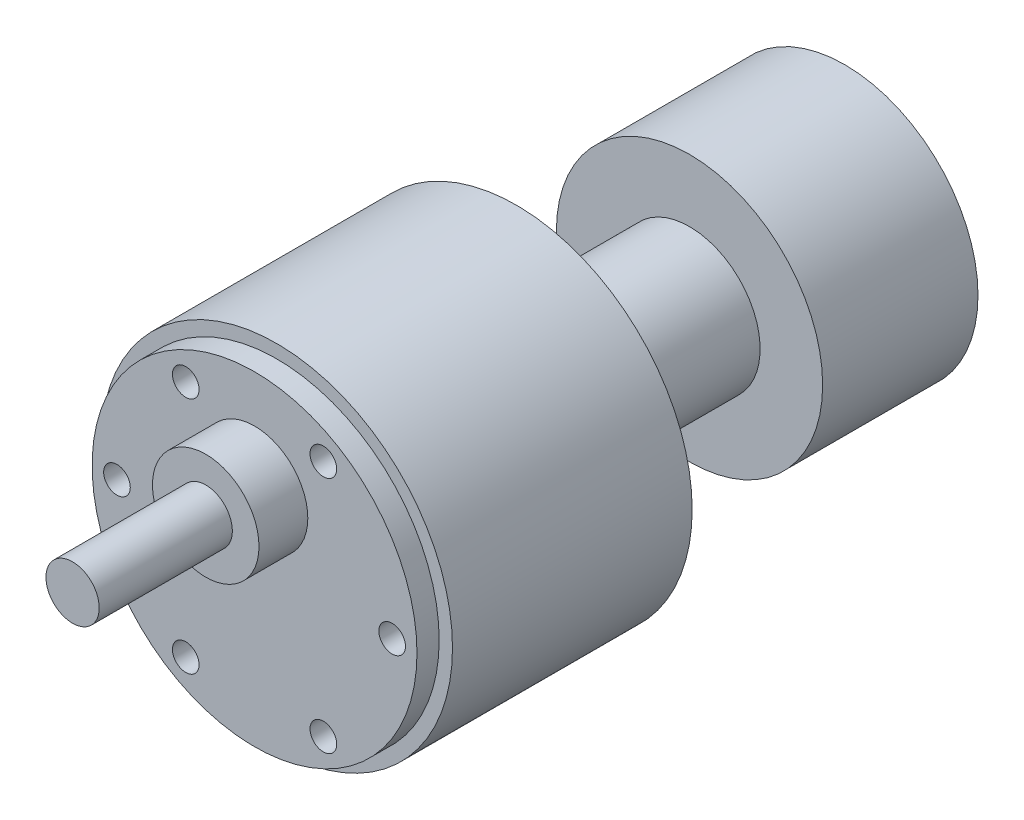
SolidWorks part; units mm, degrees
ref_plane "Front Plane" through (0, 0, 0) normal (0, 0, 1) x (1, 0, 0)
ref_plane "Top Plane" through (0, 0, 0) normal (0, 1, 0) x (1, 0, 0)
ref_plane "Right Plane" through (0, 0, 0) normal (1, 0, 0) x (0, 0, -1)
sketch "Sketch4" plane through (0, 0, 0) normal (0, 0, 1) x (1, 0, 0)
  circle A0 centre (0, 0) radius 7.9537
  dimension "D1" = 15.9075
extrude "Boss-Extrude4" add sketch "Sketch4" along normal mid plane 66.5
ref_plane "Plane3" through (0, 0, 30.75) normal (0, 0, 1) x (1, 0, 0)
sketch "Sketch5" plane through (0, 0, 30.75) normal (0, 0, 1) x (1, 0, 0)
  circle A0 centre (0, 0) radius 19.8
  circle A1 centre (0, 0) radius 18.3
  dimension "D1" = 39.6
  dimension "D2" = 36.6
extrude "Boss-Extrude5" add sketch "Sketch5" along normal blind 2.5 contours A1 region at (0, 0, 30.75)
extrude "Boss-Extrude6" add sketch "Sketch5<3>" against normal blind 27 contours A1 | A0 A1 region at (-19.24, 0, 30.75) region at (0, 0, 30.75)
sketch "Sketch5<3>" plane through (0, 0, 30.75) normal (0, 0, 1) x (1, 0, 0) same geometry as "Sketch5"
sketch "Sketch6" plane through (0, 0, -33.25) normal (0, 0, -1) x (-1, 0, 0)
  circle A0 centre (0, 0) radius 15
  dimension "D1" = 30
extrude "Boss-Extrude7" add sketch "Sketch6" against normal blind 17.5
ref_axis "Axis1" through (0, 0, 64.6975) along (0, 0, -1)
sketch "Sketch7" plane through (0, 0, 33.25) normal (0, 0, 1) x (1, 0, 0)
  circle A0 centre (0, 7) radius 6
  point P3 (0, 8.1408)
  dimension "D1" = 12
  dimension "D2" = 7
extrude "Boss-Extrude8" add sketch "Sketch7" along normal blind 5.5
ref_point "Point1"
sketch "Sketch9" plane through (0, 0, 38.75) normal (0, 0, 1) x (1, 0, 0)
  circle A0 centre (0, 7) radius 3
  dimension "D1" = 6
extrude "Boss-Extrude9" add sketch "Sketch9" along normal blind 15
sketch "Sketch10" plane through (0, 0, 33.25) normal (0, 0, 1) x (1, 0, 0)
  line L0 (-15.5, 0) -> (15.5, 0) construction
  circle A0 centre (0, 0) radius 15.5 construction
  circle A1 centre (-15.5, 0) radius 1.5
  dimension "D1" = 31
  dimension "D2" = 3
extrude "Cut-Extrude1" cut sketch "Sketch10" against normal blind 4 contours A1
pattern_circular "CirPattern1" count 6 over 360 about axis through (0, 0, 64.6975) along (0, 0, -1) of "Cut-Extrude1"
sketch "Sketch11" plane through (0, 0, 33.25) normal (0, 0, 1) x (1, 0, 0)
  line L0 (0, 18.3) -> (0, -18.3) construction
  line L1 (-18.3, 0) -> (18.3, 0) construction
  circle A0 centre (0, 0) radius 18.3 construction
  circle A1 centre (0, 0) radius 18.3 construction
sketch "Sketch12" plane through (0, 0, 38.75) normal (0, 0, 1) x (1, 0, 0)
  line L0 (0, 13) -> (0, 1) construction
  line L1 (0, 18.3) -> (0, -18.3) construction
  line L2 (6, 7) -> (-6, 7) construction
  circle A0 centre (0, 7) radius 6 construction
  circle A1 centre (0, 7) radius 6 construction
sketch "Sketch13" plane through (0, 0, 53.75) normal (0, 0, 1) x (1, 0, 0)
  line L0 (0, 10) -> (0, 4) construction
  line L1 (0, 18.3) -> (0, -18.3) construction
  line L2 (-3, 7) -> (3, 7) construction
  line L3 (6, 7) -> (-6, 7) construction
  circle A0 centre (0, 7) radius 3 construction
  circle A1 centre (0, 7) radius 3 construction
